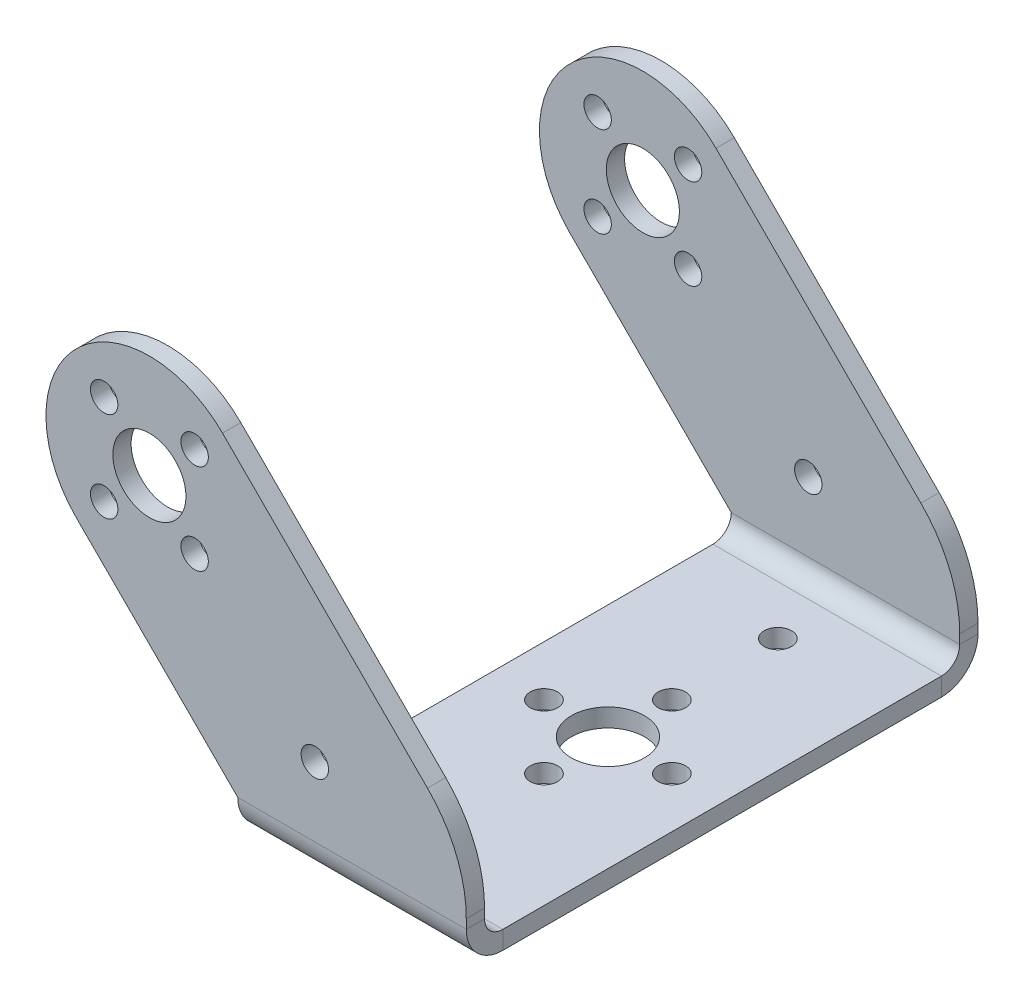
SolidWorks part; units mm, degrees
note: The reader was unsure of these and kept them because the rebuilt part matched: flange length of "Edge-Flange1".
material "6063-T4"
ref_plane "Plan de face" through (0, 0, 0) normal (0, 0, 1) x (1, 0, 0)
ref_plane "Plan de dessus" through (0, 0, 0) normal (0, 1, 0) x (1, 0, 0)
ref_plane "Plan de droite" through (0, 0, 0) normal (1, 0, 0) x (0, 0, -1)
ref_plane "Plan1" through (0, 0, 0) normal (0, 0, -1) x (-1, 0, 0)
sketch "Sketch8" plane through (0, 0, 0) normal (0, 0, 1) x (1, 0, 0)
  line L0 (-30.1777, 33.6848) -> (0, 0) construction
  line L1 (-12.5, 0) -> (12.5, 0)
  line L2 (-12.5, 0) -> (-30.1777, 17.6777)
  line L3 (8.253, 11.2612) -> (-14.1705, 33.6848)
  line L4 (12.5, 1.0082) -> (12.5, 0)
  line L5 (-22.1741, 37) -> (-22.1741, 0) construction
  arc A0 (-30.1777, 17.6777) -> (-14.1705, 33.6848) centre (-22.1741, 25.6812) cw
  arc A1 (8.253, 11.2612) -> (12.5, 1.0082) centre (-2, 1.0082) cw
  dimension "D5" = 14.5
  dimension "D1" = 25
  dimension "D3" = 45
  dimension "D2" = 25
  dimension "D4" = 37
base flange "Base-Flange1" sketch "Sketch8" thickness 2 reverse thickness direction no parameters "D1"=2
edge flange "Edge-Flange1" sketch "Sketch14" flange angle 90 flange length 26 flange position bend outside bend radius 2 thickness 2 relief rectangular parameters "D6"=10
sketch "Sketch14" plane through (0, 0, -2) normal (0, -1, 0) x (-1, 0, 0)
  line L0 (12.5, 0) -> (-12.5, 0) construction
  line L1 (12.5, 0) -> (-12.5, 0)
  line L2 (-12.5, 0) -> (-12.5, 26)
  line L3 (-12.5, 26) -> (12.5, 26)
  line L4 (12.5, 26) -> (12.5, 0)
bend "EdgeBend1" bend radius 2 bend angle 90 parameters "D5"=1
sketch "Sketch19" plane through (0, 0, 0) normal (0, 0, 1) x (1, 0, 0)
  circle A0 centre (-22.1741, 25.6812) radius 4
  dimension "D1" = 8
extrude "Cut-Extrude2" cut sketch "Sketch19" against normal through all normal cut yes
hole_wizard "M3x0.5 Tapped Hole1" positions "Sketch21" profile "Sketch20" tap size "M3x0.5" standard "ANSI Metric" end condition through all
sketch "Sketch21" plane through (0, 0, 0) normal (0, 0, 1) x (1, 0, 0)
  line L0 (-27.1238, 30.631) -> (-17.2244, 20.7315) construction
  line L2 (-17.2244, 30.631) -> (-27.1238, 20.7315) construction
  line L4 (-4.0722, 7.5793) -> (-17.2244, 20.7315) construction
  line L6 (-30.1777, 17.6777) -> (-12.5, 0) construction
  circle A0 centre (-22.1741, 25.6812) radius 7 construction
  point P0 (-27.1238, 30.631)
  point P2 (-27.1238, 20.7315)
  point P4 (-17.2244, 20.7315)
  point P6 (-17.2244, 30.631)
  point P22 (-22.1741, 25.6812)
  point P30 (-4.0722, 7.5793)
  dimension "D1" = 14
  dimension "D2" = 18.6
sketch "Sketch20" plane through (-27.1238, 30.631, 0) normal (1, 0, 0) x (0, -1, 0)
  line L0 (0, 0) -> (0, 28)
  line L1 (0, 28) -> (1.5, 28)
  line L2 (1.5, 28) -> (1.5, 0)
  line L5 (1.5, 0) -> (0, 0)
  line L11 (0, -6.35) -> (0, 107.95) construction
  dimension "Thread Major Dia." = 3
  dimension "Thru Tap Drill Depth" = 28
mirror "Mirror1" about plane through (12.5, -4, -28) normal (0, 0, 1) of bodies 153
bend "MirrorBend1" bend radius 2 bend angle 90 parameters "D5"=2
sketch "Sketch22" plane through (0, -2, 0) normal (0, 1, 0) x (1, 0, 0)
  line L0 (-12.5, 28) -> (12.5, 28) construction
  line L1 (-12.5, 4) -> (-12.5, 52) construction
  line L2 (12.5, 52) -> (12.5, 4) construction
  circle A0 centre (0, 28) radius 4
  dimension "D1" = 8
extrude "Cut-Extrude3" cut sketch "Sketch22" against normal through all normal cut yes
hole_wizard "M3x0.5 Tapped Hole2" positions "Sketch24" profile "Sketch23" tap size "M3x0.5" standard "ANSI Metric" end condition through all
sketch "Sketch24" plane through (0, -2, 0) normal (0, 1, 0) x (1, 0, 0)
  line L2 (7, 28) -> (-7, 28) construction
  line L4 (0, 21) -> (0, 35) construction
  line L5 (0, 46.6) -> (0, 9.4) construction
  circle A0 centre (0, 28) radius 7 construction
  point P0 (7, 28)
  point P2 (-7, 28)
  point P4 (0, 35)
  point P6 (0, 21)
  point P8 (0, 9.4)
  point P10 (0, 46.6)
  point P28 (0, 28)
  point P33 (0, 28)
  dimension "D2" = 14
  dimension "D1" = 18.6
sketch "Sketch23" plane through (7, -2, -28) normal (1, 0, 0) x (0, 0, 1)
  line L0 (0, 0) -> (0, 2)
  line L1 (0, 2) -> (1.5, 2)
  line L2 (1.5, 2) -> (1.5, 0)
  line L5 (1.5, 0) -> (0, 0)
  line L11 (0, -6.35) -> (0, 107.95) construction
  dimension "Thread Major Dia." = 3
  dimension "Thru Tap Drill Depth" = 2
sketch "Bend-Lines1" [suppressed] plane through (0, 0, 0) normal (0, 1, 0) x (1, 0, 0)
sketch "Bounding-Box1" [suppressed] plane through (0, 0, 0) normal (0, 1, 0) x (1, 0, 0)
sheet metal parameters "Sheet-Metal48" thickness 2 parameters "D1"=1
flat pattern "Flat-Pattern56" [suppressed]
sketch "Bend-Lines3" plane through (0, 0, 0) normal (0, 1, 0) x (1, 0, 0)
sketch3d "Bounding-Box3" [suppressed]
  line L0 (-12.5, -50, 0) -> (-12.5, 12.5, 0) construction
  line L1 (12.5, -50, 0) -> (12.5, 12.5, 0) construction
  line L2 (-12.5, -50, 0) -> (12.5, -50, 0) construction
  line L3 (-12.5, 12.5, 0) -> (12.5, 12.5, 0) construction
sheet metal parameters "Sheet-Metal49" thickness 2 parameters "D1"=1
flat pattern "Flat-Pattern56"
sketch "Bend-Lines3" plane through (0, 0, 0) normal (0, 0, 1) x (1, 0, 0)
  line L0 (-12.5, 0.8219) -> (12.5, 0.8219) construction
  line L1 (-12.5, 0.8219) -> (12.5, 0.8219) construction
sketch3d "Bounding-Box3" [suppressed]
  line L0 (12.5, -100.3562, 0) -> (12.5, 12.5, 0) construction
  line L1 (-12.5, -100.3562, 0) -> (-12.5, 12.5, 0) construction
  line L2 (12.5, -100.3562, 0) -> (-12.5, -100.3562, 0) construction
  line L3 (12.5, 12.5, 0) -> (-12.5, 12.5, 0) construction
bend of the flat pattern "Flatten-<EdgeBend1>1"
sheet metal parameters "Sheet-Metal52" thickness 2 parameters "D1"=1
flat pattern "Flat-Pattern56"
sketch "Bend-Lines3" plane through (0, 0, 0) normal (0, 0, 1) x (1, 0, 0)
  line L0 (-12.5, -1.1781) -> (12.5, -1.1781) construction
  line L1 (-12.5, -1.1781) -> (12.5, -1.1781) construction
  line L2 (-12.5, -52.5343) -> (12.5, -52.5343) construction
  line L3 (-12.5, -52.5343) -> (12.5, -52.5343) construction
sketch3d "Bounding-Box3" [suppressed]
  line L0 (12.5, 12.5, 0) -> (12.5, -164.2123, 0) construction
  line L1 (-12.5, 12.5, 0) -> (-12.5, -164.2123, 0) construction
  line L2 (12.5, 12.5, 0) -> (-12.5, 12.5, 0) construction
  line L3 (12.5, -164.2123, 0) -> (-12.5, -164.2123, 0) construction
bend of the flat pattern "Flatten-<EdgeBend1>1"
sheet metal parameters "Sheet-Metal53" thickness 2 parameters "D1"=1
flat pattern "Flat-Pattern56"
sketch "Bend-Lines3" plane through (0, 0, 0) normal (0, 0, 1) x (1, 0, 0)
  line L0 (-12.5, -1.1781) -> (12.5, -1.1781) construction
  line L1 (-12.5, -1.1781) -> (12.5, -1.1781) construction
  line L2 (-12.5, -52.5343) -> (12.5, -52.5343) construction
  line L3 (-12.5, -52.5343) -> (12.5, -52.5343) construction
sketch3d "Bounding-Box3" [suppressed]
  line L0 (12.5, 12.5, 0) -> (12.5, -164.2123, 0) construction
  line L1 (-12.5, 12.5, 0) -> (-12.5, -164.2123, 0) construction
  line L2 (12.5, 12.5, 0) -> (-12.5, 12.5, 0) construction
  line L3 (12.5, -164.2123, 0) -> (-12.5, -164.2123, 0) construction
bend of the flat pattern "Flatten-<EdgeBend1>1"
sheet metal parameters "Sheet-Metal54" thickness 2 parameters "D1"=1
flat pattern "Flat-Pattern56" [suppressed]
sketch "Bend-Lines4" plane through (0, 0, 0) normal (0, 0, 1) x (1, 0, 0)
  line L0 (-12.5, -1.1781) -> (12.5, -1.1781) construction
  line L1 (-12.5, -1.1781) -> (12.5, -1.1781) construction
  line L2 (-12.5, -52.5343) -> (12.5, -52.5343) construction
  line L3 (-12.5, -52.5343) -> (12.5, -52.5343) construction
sketch3d "Bounding-Box4" [suppressed]
  line L0 (12.5, 12.5, 0) -> (12.5, -164.2123, 0) construction
  line L1 (-12.5, 12.5, 0) -> (-12.5, -164.2123, 0) construction
  line L2 (12.5, 12.5, 0) -> (-12.5, 12.5, 0) construction
  line L3 (12.5, -164.2123, 0) -> (-12.5, -164.2123, 0) construction
bend of the flat pattern "Flatten-<EdgeBend1>1"
bend of the flat pattern "Flatten-<MirrorBend1>3"
sheet metal parameters "Sheet-Metal55" thickness 2 parameters "D1"=1
flat pattern "Flat-Pattern56"
sketch "Bend-Lines4" plane through (0, 0, 0) normal (0, 0, 1) x (1, 0, 0)
  line L0 (-12.5, -2.3562) -> (12.5, -2.3562) construction
  line L1 (-12.5, -2.3562) -> (12.5, -2.3562) construction
  line L2 (-12.5, -55.0686) -> (12.5, -55.0686) construction
  line L3 (-12.5, -55.0686) -> (12.5, -55.0686) construction
sketch3d "Bounding-Box4" [suppressed]
  line L0 (34.6741, 11.3188, 0) -> (34.6741, -120.106, 0) construction
  line L1 (-11.3187, 11.3188, 0) -> (-11.3187, -120.106, 0) construction
  line L2 (34.6741, 11.3188, 0) -> (-11.3187, 11.3188, 0) construction
  line L3 (34.6741, -120.106, 0) -> (-11.3187, -120.106, 0) construction
bend of the flat pattern "Flatten-<EdgeBend1>1"
bend of the flat pattern "Flatten-<MirrorBend1>2"
sheet metal parameters "Sheet-Metal56" thickness 2 parameters "D1"=1
flat pattern "Flat-Pattern56"
sketch "Bend-Lines4" plane through (0, 0, 0) normal (0, 0, 1) x (1, 0, 0)
  line L0 (-12.5, -105.5343) -> (12.5, -105.5343) construction
  line L1 (-12.5, -1.1781) -> (12.5, -1.1781) construction
  line L2 (-12.5, -105.5343) -> (12.5, -105.5343) construction
  line L3 (-12.5, -1.1781) -> (12.5, -1.1781) construction
sketch3d "Bounding-Box4" [suppressed]
  line L0 (33.8457, 12.4903, 0) -> (33.8457, -172.2221, 0) construction
  line L1 (-12.4903, 12.4903, 0) -> (-12.4903, -172.2221, 0) construction
  line L2 (33.8457, 12.4903, 0) -> (-12.4903, 12.4903, 0) construction
  line L3 (33.8457, -172.2221, 0) -> (-12.4903, -172.2221, 0) construction
bend of the flat pattern "Flatten-<EdgeBend1>2"
bend of the flat pattern "Flatten-<MirrorBend1>1"
equation "\"D7@Edge-Flange1\"=52/2"
equation "\"D4@Sketch8\"=39-2"
